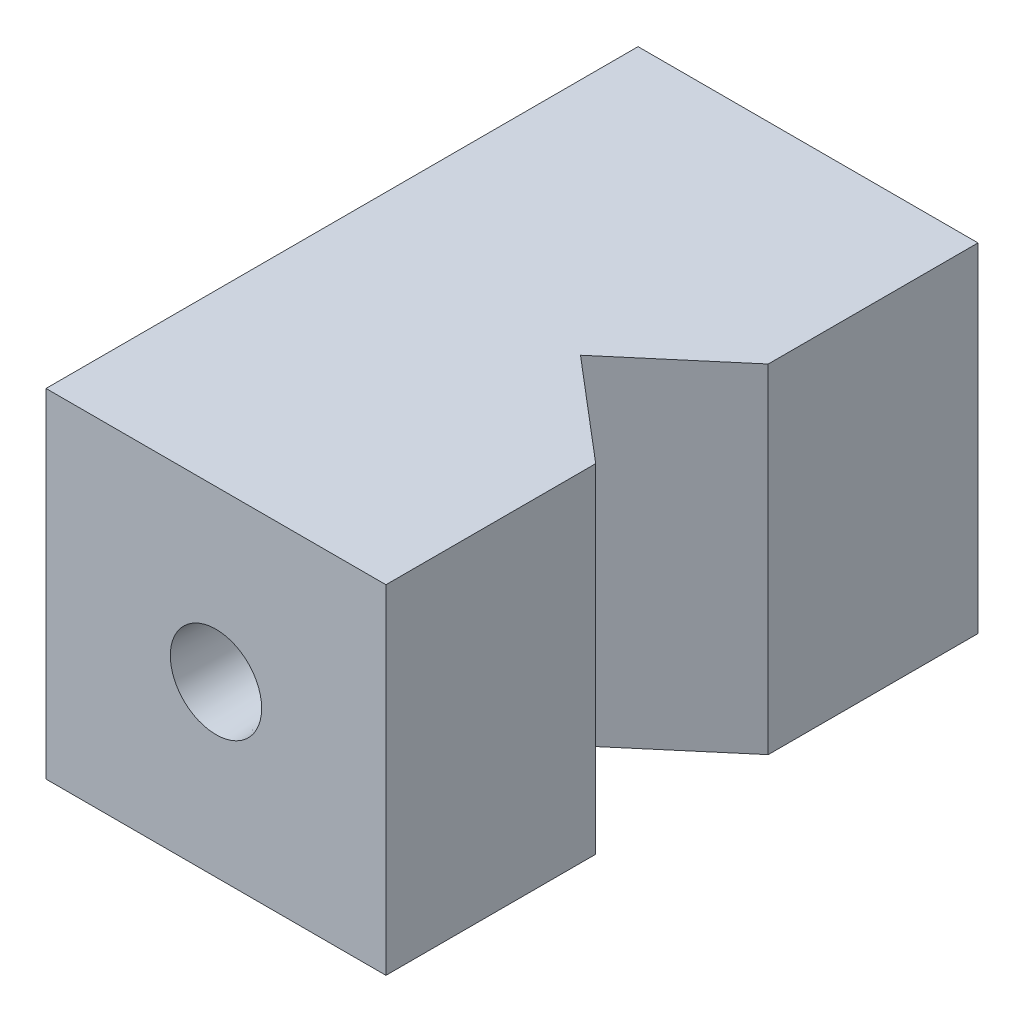
SolidWorks part; units mm, degrees
ref_plane "Front Plane" through (0, 0, 0) normal (0, 0, 1) x (1, 0, 0)
ref_plane "Top Plane" through (0, 0, 0) normal (0, 1, 0) x (1, 0, 0)
ref_plane "Right Plane" through (0, 0, 0) normal (1, 0, 0) x (0, 0, -1)
sketch "Sketch2" plane through (0, 0, 0) normal (0, 1, 0) x (1, 0, 0)
  circle A0 centre (0, 0) radius 30
  dimension "D1" = 60
extrude "Boss-Extrude1" add sketch "Sketch2" along normal blind 20 from offset 0.2
sketch "Sketch3" plane through (0, 20.2, 0) normal (0, 1, 0) x (1, 0, 0)
  line L0 (-24.367, 17.5) -> (-19.1, 17.5)
  line L1 (-19.1, 17.5) -> (-19.1, 21.5)
  line L2 (-19.1, 21.5) -> (0, 21.5)
  line L3 (0, 21.5) -> (0, 17.5)
  line L4 (0, -21.5) -> (0, -17.5)
  line L5 (0, -21.5) -> (-19.1, -21.5)
  line L6 (-19.1, -21.5) -> (-19.1, -17.5)
  line L7 (-19.1, -17.5) -> (-24.367, -17.5)
  line L9 (-13.1, 13.5) -> (-20, 13.5)
  line L10 (-20, 13.5) -> (-20, 8.5)
  line L11 (-20, 8.5) -> (-12, 8.5)
  line L12 (-12, 8.5) -> (-12, 2.5)
  line L13 (-12, 2.5) -> (-20, 2.5)
  line L14 (-20, 2.5) -> (-20, -2.5)
  line L15 (-20, -2.5) -> (-12, -2.5)
  line L16 (-12, -2.5) -> (-12, -8.5)
  line L17 (-12, -8.5) -> (-20, -8.5)
  line L18 (-20, -8.5) -> (-20, -13.5)
  line L22 (-20, -13.5) -> (-13.1, -13.5)
  line L23 (-2, 5.1) -> (-2, 9.0619)
  line L25 (-2, -5.1) -> (-2, -9.0619)
  line L28 (-2, -9.0619) -> (-2, -17.5)
  line L29 (-2, 9.0619) -> (-2, 17.5)
  line L30 (0, 17.5) -> (0, -17.5) construction
  line L31 (-2, 17.5) -> (0, 17.5)
  line L32 (-2, -17.5) -> (0, -17.5)
  line L33 (-2, 5.1) -> (-8, 0)
  line L34 (-8, 0) -> (-2, -5.1)
  circle A0 centre (0, 0) radius 30 construction
  arc A1 (0, 17.5) -> (0, -17.5) centre (0, 0) cw
  arc A2 (-24.367, 17.5) -> (-24.367, -17.5) centre (0, 0) ccw
  arc A4 (0, 5) -> (0, -5) centre (0, 0) ccw construction
  arc A5 (-13.1, 13.5) -> (-2, 9.0619) centre (-13.1, -2.6) cw
  arc A7 (-13.1, -13.5) -> (-2, -9.0619) centre (-13.1, 2.6) ccw
  point P35 (-20, 0)
  dimension "D9" = 13.1
  dimension "D7" = 5.1
  dimension "D12" = 5
  dimension "D10" = 16.1
  dimension "D2" = 4
  dimension "D3" = 35
  dimension "D4" = 4
  dimension "D5" = 5
  dimension "D6" = 5
  dimension "D8" = 19.1
  dimension "D11" = 8
  dimension "D13" = 2
  dimension "D14" = 5.1
  dimension "D15" = 20
  dimension "D16" = 8
extrude "Cut-Extrude2" cut sketch "Sketch3" against normal through all contours A1 region at (5.8119, 20.2, 0)
sketch "Sketch4" plane through (0, 20.2, 0) normal (0, 1, 0) x (1, 0, 0)
  line L0 (-2, 17.5) -> (-2, -17.5)
  line L1 (-2, -17.5) -> (-24.367, -17.5)
  line L3 (-30, -30) -> (30, -30)
  line L4 (30, -30) -> (30, 30)
  line L5 (30, 30) -> (-30, 30)
  line L7 (-24.367, 17.5) -> (-2, 17.5)
  line L8 (-24.367, 17.5) -> (-24.367, -17.5)
  line L9 (-30, 30) -> (-30, -30)
  circle A0 centre (0, 0) radius 30 construction
extrude "Cut-Extrude3" cut sketch "Sketch4" against normal through all
sketch "Sketch11" plane through (0, 20.2, 0) normal (0, 1, 0) x (1, 0, 0)
  line L1 (-24.367, 17.5) -> (-22.097, 17.5)
  line L2 (-24.367, 17.5) -> (-24.367, -20)
  line L3 (-24.367, -20) -> (-22.097, -20)
  line L4 (-22.097, 17.5) -> (-22.097, -20)
  dimension "D1" = 2.27
extrude "Cut-Extrude4" cut sketch "Sketch11" against normal through all
hole_wizard "Hole1" positions "Sketch12" profile "Sketch13" legacy
sketch "Sketch12" plane through (0, 0, 17.5) normal (0, 0, 1) x (1, 0, 0)
  line L0 (-22.097, 0.2) -> (-2, 0.2) construction
  line L1 (-22.097, 0.2) -> (-22.097, 20.2) construction
  point P0 (-12.0485, 10.2)
  point P5 (-12.0485, 0.2)
  point P8 (-22.097, 10.2)
sketch "Sketch13" plane through (-12.0485, 10.2, 17.5) normal (1, 0, 0) x (0, -1, 0)
  line L0 (0, 0) -> (0, 10)
  line L1 (0, 10) -> (2.4, 10)
  line L2 (2.4, 10) -> (2.4, 6)
  line L3 (2.4, 6) -> (2.7, 6)
  line L4 (2.7, 6) -> (2.7, 0)
  line L5 (2.7, 0) -> (0, 0)
  line L6 (0, 110) -> (0, -10) construction
  dimension "Diameter" = 4.8
  dimension "Depth" = 10
  dimension "C-Bore Diameter" = 5.4
  dimension "C-Bore Depth" = 6
chamfer "Chamfer1" distance 6 distance2 0.3 1 edges at (-9.3485, 10.2, 11.5) first distance on face at (-9.3485, 10.2, 11.5)
mirror "Mirror1" about plane through (0, 0, 0) normal (0, 0, 1) of "Chamfer1", "Hole1"
